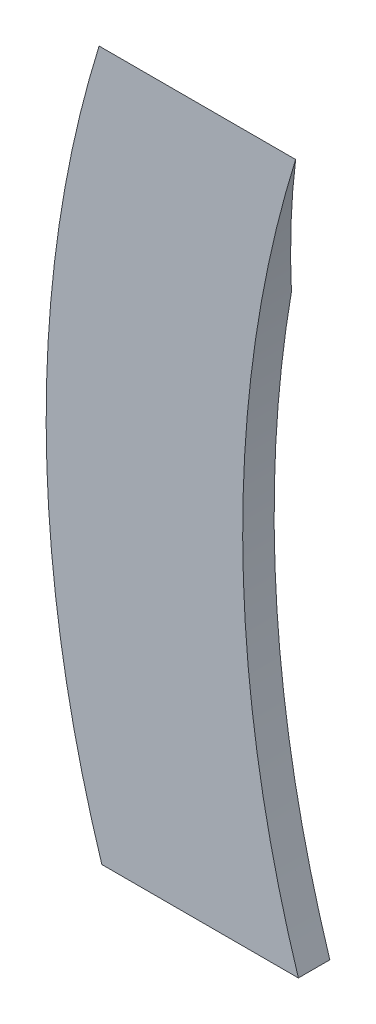
SolidWorks part; units mm, degrees
ref_plane "前视基准面" through (0, 0, 0) normal (0, 0, 1) x (1, 0, 0)
ref_plane "上视基准面" through (0, 0, 0) normal (0, 1, 0) x (1, 0, 0)
ref_plane "右视基准面" through (0, 0, 0) normal (1, 0, 0) x (0, 0, -1)
sketch "草图1" plane through (0, 0, 0) normal (0, 0, 1) x (1, 0, 0)
  line L0 (-0.3505, 90) -> (24.6495, 90)
  line L1 (0, 0) -> (25, 0)
  arc A8 (24.6495, 90) -> (25, 0) centre (167.9144, 45.5573) ccw
  arc A9 (0, 0) -> (-0.3505, 90) centre (142.9144, 45.5573) cw
  dimension "D6" = 90
  dimension "D19" = 150
  dimension "D20" = 150
  dimension "D3" = 25
extrude "凸台-拉伸1" add sketch "草图1" along normal blind 4
sketch "草图2" plane through (0, 0, 0) normal (1, 0, 0) x (0, 0, -1)
  line L0 (-4, 90) -> (0, 71.1815)
  line L1 (0, 0) -> (0, 90) construction
  line L2 (0, 71.1815) -> (0, 90)
  line L3 (0, 90) -> (-4, 90)
  dimension "D1" = 12
extrude "切除-拉伸1" cut sketch "草图2" against normal through all and the other way through all
sketch "草图3" plane through (0, 0, 0) normal (1, 0, 0) x (0, 0, -1)
  line L0 (-3, 70) -> (-1, 70)
  line L1 (-1, 70) -> (-1, 20)
  line L2 (-1, 20) -> (-3, 20)
  line L3 (-3, 20) -> (-3, 70)
  line L4 (-2, 0) -> (-2, 26.0633) construction
  line L5 (-4, 90) -> (-4, 0) construction
  line L6 (-4, 0) -> (0, 0) construction
  dimension "D1" = 20
  dimension "D2" = 50
  dimension "D3" = 1
extrude "切除-拉伸2" cut sketch "草图3" against normal through all and the other way blind 12
sketch "草图4" plane through (0, 0, 0) normal (0, 0, -1) x (-1, 0, 0)
  arc A0 (0, 0) -> (4.8807, 71.1815) centre (-142.9144, 45.5573) ccw construction
  spline S0 degree 3 poles (11.7956, 56.4603) (5.708, 59.1396) (0.8722, 53.3747) (-0.3045, 46.7149) (0.4101, 39.8988) (-1.708, 32.978) (3.4671, 30.9496) (6.581, 28.4473) (12.0189, 31.4667) (10.2572, 40.5757) (10.5733, 48.2191) (11.7956, 56.4603) (5.708, 59.1396) (0.8722, 53.3747) knots -0.316524 -0.145081 -0.061723 0 0.085366 0.216378 0.293679 0.395978 0.471646 0.504855 0.563787 0.683476 0.854919 0.938277 1 1.085366 1.216378 1.293679 only from (6.5664, 58.0267) to (6.5664, 58.0267)
extrude "切除-拉伸3" [suppressed] cut sketch "草图4" against normal blind 2
